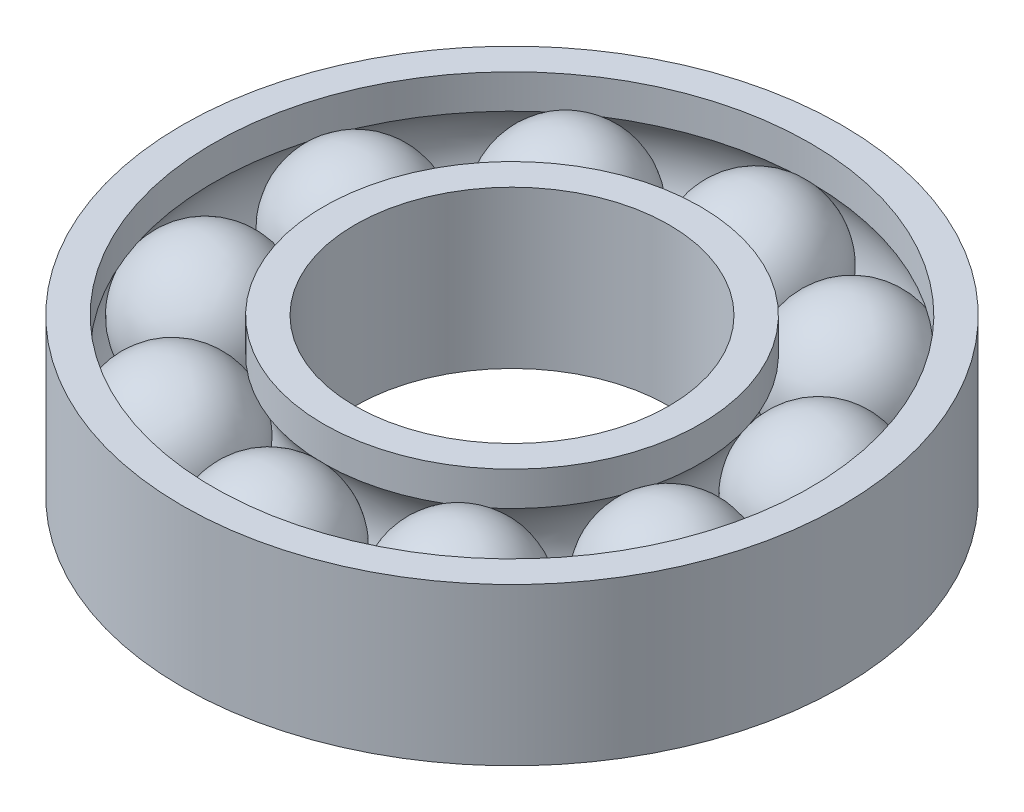
SolidWorks part; units mm, degrees
ref_plane "Front Plane" through (0, 0, 0) normal (0, 0, 1) x (1, 0, 0)
ref_plane "Top Plane" through (0, 0, 0) normal (0, 1, 0) x (1, 0, 0)
ref_plane "Right Plane" through (0, 0, 0) normal (1, 0, 0) x (0, 0, -1)
sketch "Sketch1" plane through (0, 0, 0) normal (1, 0, 0) x (0, 0, -1)
  line L0 (0, -25) -> (0, 25)
  line L1 (95, 14.1421) -> (95, 25)
  line L2 (50, -25) -> (60, -25)
  line L3 (50, -25) -> (50, 25)
  line L4 (50, 25) -> (60, 25)
  line L5 (60, -25) -> (60, -14.1421)
  line L6 (50, -25) -> (60, 25) construction
  line L7 (50, 25) -> (60, -25) construction
  line L8 (95, -25) -> (105, -25)
  line L9 (95, -25) -> (95, -14.1421)
  line L10 (95, 25) -> (105, 25)
  line L11 (105, -25) -> (105, 25)
  line L12 (95, -25) -> (105, 25) construction
  line L13 (95, 25) -> (105, -25) construction
  line L14 (60, 14.1421) -> (60, 25)
  arc A1 (60, 14.1421) -> (60, -14.1421) centre (77.5, 0) ccw
  arc A2 (95, -14.1421) -> (95, 14.1421) centre (77.5, 0) ccw
  point P0 (55, 0)
  point P4 (0, 0)
  point P10 (100, 0)
  dimension "D2" = 45
  dimension "D1" = 50
  dimension "D3" = 10
  dimension "D4" = 50
  dimension "D5" = 10
sketch "Sketch2" plane through (0, 0, 0) normal (1, 0, 0) x (0, 0, -1)
  line L0 (95, -25) -> (105, 25) construction
  line L1 (55, 0) -> (100, 0)
  arc A0 (55, 0) -> (100, 0) centre (77.5, 0) cw
revolve "Revolve1" add sketch "Sketch2" angle 360 about L1
revolve "Revolve2" add sketch "Sketch1" angle 360 about L0 region at (0, 0, -100.7135) region at (0, 0, -54.2865)
ref_axis "Axis1" through (0, -8.25, 0) along (0, 1, 0)
pattern_circular "CirPattern2" count 10 over 360 about axis through (0, -8.25, 0) along (0, 1, 0) of bodies 101
